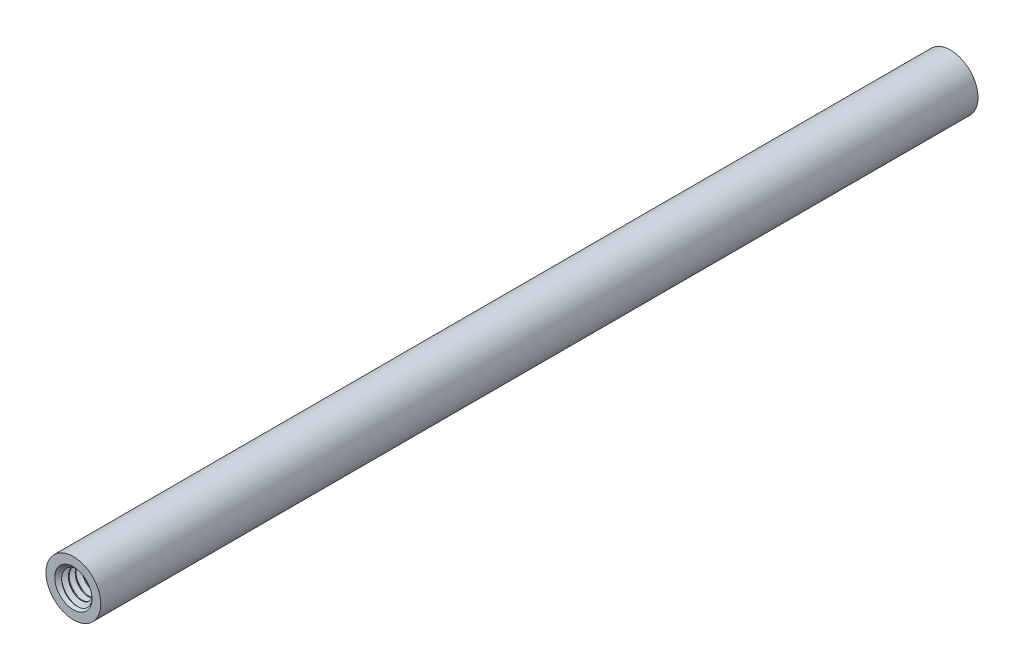
SolidWorks part; units mm, degrees
ref_plane "Front Plane" through (0, 0, 0) normal (0, 0, 1) x (1, 0, 0)
ref_plane "Top Plane" through (0, 0, 0) normal (0, 1, 0) x (1, 0, 0)
ref_plane "Right Plane" through (0, 0, 0) normal (1, 0, 0) x (0, 0, -1)
sketch "Sketch3" plane through (0, 0, 0) normal (1, 0, 0) x (0, 0, -1)
  line L0 (-50.8, 0) -> (50.8, 0) construction
  line L1 (0, 3.175) -> (0, -3.175) construction
  line L2 (-50.8, 2.0828) -> (-50.8, -2.0828) construction
  point P2 (39.6875, 0)
  point P3 (-39.6875, 0)
  dimension "D1" = 11.1125
  dimension "Length" = 101.6
  dimension "Min Thread Length" = 11.1125
  dimension "Thread Dia" = 4.1656
  dimension "OD" = 6.35
ref_axis "Axis1" through (0, 3.175, 0) along (0, -1, 0)
sketch "Sketch10" plane through (0, 0, 0) normal (1, 0, 0) x (0, 0, -1)
  line L0 (50.8, 2.0828) -> (39.6875, 2.0828)
  line L1 (-50.8, 2.0828) -> (-39.6875, 2.0828)
  line L2 (39.6875, 2.0828) -> (39.6875, -2.0828)
  line L3 (-50.8, -2.0828) -> (-39.6875, -2.0828)
  line L4 (-39.6875, 2.0828) -> (-39.6875, -2.0828)
  line L5 (39.6875, -2.0828) -> (50.8, -2.0828)
sketch "Sketch13" plane through (0, 0, 0) normal (0, 0, 1) x (1, 0, 0)
  circle A0 centre (0, 0) radius 2.0828
extrude "Boss-Extrude1" add sketch "Sketch13" against normal up to vertex (-39.6875 mm away) from vertex at 50.8 starting at point (0, 0, 50.8)
sketch "Sketch14" plane through (0, 0, 50.8) normal (0, 0, 1) x (1, 0, 0)
  circle A1 centre (0, 0) radius 2.0828
  circle A2 centre (0, 0) radius 2.0828
  dimension "D1" = 0
curve "Helix/Spiral2" pitch 0.7937 height 11.9062 turns 15 parameters "Pitch"=0.7937
sketch "Sketch15" plane through (0, 0, 0) normal (1, 0, 0) x (0, 0, -1)
  line L0 (-51.4945, 2.0828) -> (-50.8, 2.0828)
  line L1 (-51.4945, 2.0828) -> (-51.1969, 1.5672)
  line L2 (-51.1969, 1.5672) -> (-51.0977, 1.5672)
  line L3 (-51.0977, 1.5672) -> (-50.8, 2.0828)
  line L4 (-51.1473, 1.5672) -> (-51.1473, 2.0828) construction
  line L5 (-51.3457, 1.825) -> (-50.9488, 1.825) construction
  dimension "D1" = 60
  dimension "D2" = 0.0992
  dimension "D3" = 0.3969
sweep "Cut-Sweep1" cut profiles "Sketch15" path "Helix/Spiral2" align with end faces yes
sketch "Sketch16" plane through (0, 0, 50.8) normal (0, 0, 1) x (1, 0, 0)
  circle A2 centre (0, 0) radius 2.159
  circle A3 centre (0, 0) radius 2.159
  dimension "D1" = 0.0762
extrude "Boss-Extrude2" add sketch "Sketch16" against normal through all draft 45
pattern_circular "CirPattern1" count 2 over 180 about axis through (0, 3.175, 0) along (0, -1, 0) of bodies 113
sketch "Sketch1" plane through (0, 0, 0) normal (0, 0, 1) x (1, 0, 0)
  circle A1 centre (0, 0) radius 2.0828 construction
  circle A2 centre (0, 0) radius 3.175
extrude "Extrude1" add sketch "Sketch1" along normal up to vertex (50.8 mm away) and the other way up to vertex (50.8 mm away) up to point (0, 0, 50.8) other way up to point (0, 0, -50.8)
combine bodies "Combine1" operation type subtract main body 101 bodies to subtract 114 113
equation "\"D1@Sketch3\" = \"Min Thread Length@Sketch3\""
equation "\"D3@Helix/Spiral2\" = \"Min Thread Length@Sketch3\"+\"Pitch@Helix/Spiral2\""
equation "\"D2@Sketch15\" = \"Pitch@Helix/Spiral2\"*.125"
equation "\"D3@Sketch15\" = \"Pitch@Helix/Spiral2\"*.5"
